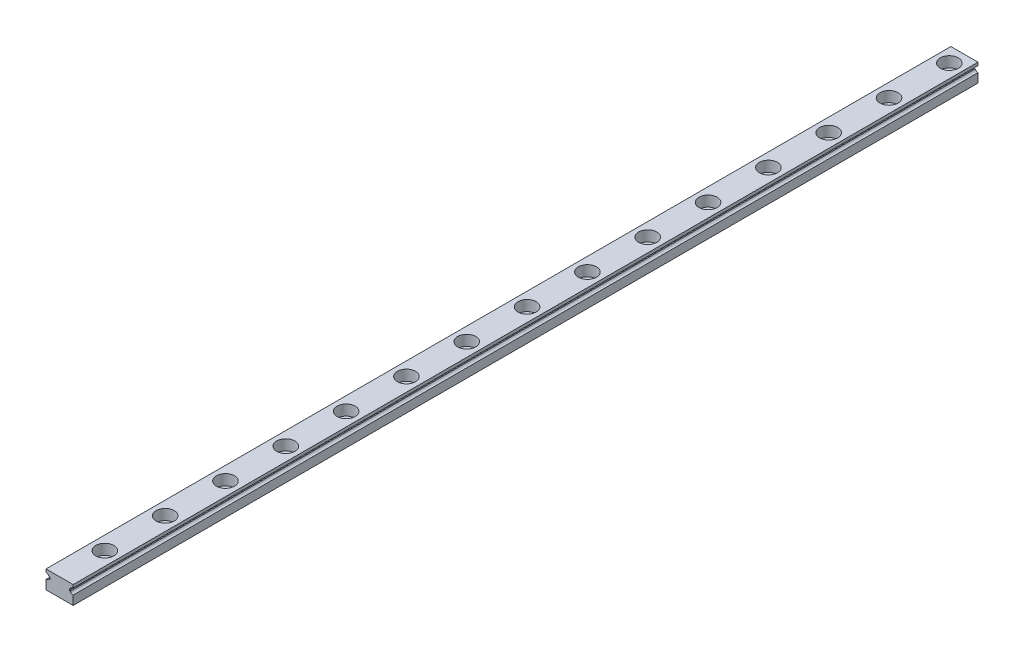
SolidWorks part; units mm, degrees
ref_plane "Спереди" through (0, 0, 0) normal (0, 0, 1) x (1, 0, 0)
ref_plane "Сверху" through (0, 0, 0) normal (0, 1, 0) x (1, 0, 0)
ref_plane "Справа" through (0, 0, 0) normal (1, 0, 0) x (0, 0, -1)
sketch "Sketch1" plane through (0, 0, 0) normal (0, 0, 1) x (1, 0, 0)
  line L0 (0, 0) -> (0, 5.7299) construction
  line L1 (-4.5, -3) -> (4.5, -3)
  line L2 (-4.5, -3) -> (-4.5, 0)
  line L3 (-4.5, 3) -> (4.5, 3)
  line L4 (4.5, -3) -> (4.5, 0)
  line L5 (-4.5, -3) -> (4.5, 3) construction
  line L6 (-4.5, 3) -> (4.5, -3) construction
  line L7 (-4.5, 2) -> (-4.5, 3)
  line L8 (-3.564, 0.648) -> (-3.2351, 0.648)
  line L9 (3.564, 0.648) -> (3.2351, 0.648)
  line L10 (-3.564, 1.352) -> (-3.2351, 1.352)
  line L11 (-3.2351, 0.648) -> (-3.2351, 1.352)
  line L12 (3.2351, 0.648) -> (3.2351, 1.352)
  line L13 (3.564, 1.352) -> (3.2351, 1.352)
  line L14 (4.5, 2) -> (4.5, 3)
  arc A0 (-3.564, 1.352) -> (-4.5, 2) centre (-4.5, 1) ccw
  arc A1 (-4.5, 0) -> (-3.564, 0.648) centre (-4.5, 1) ccw
  arc A2 (4.5, 0) -> (3.564, 0.648) centre (4.5, 1) cw
  arc A3 (3.564, 1.352) -> (4.5, 2) centre (4.5, 1) cw
  point P0 (0, 0)
  dimension "D3" = 1
  dimension "D1" = 9
  dimension "D2" = 6
  dimension "D4" = 2
extrude "Extrude1" add sketch "Sketch1" along normal blind 300
sketch "Sketch2" plane through (0, 3, 0) normal (0, 1, 0) x (1, 0, 0)
  line L0 (4.5, 0) -> (-4.5, 0) construction
  circle A0 centre (0, -5) radius 1.75
  circle A1 centre (0, -5) radius 3
  dimension "D1" = 3.5
  dimension "D2" = 6
  dimension "D3" = 5
extrude "Extrude2" cut sketch "Sketch2" against normal blind 3.5 contours A1
extrude "Extrude3" cut sketch "Sketch" against normal through all contours A0
sketch "Sketch" plane through (0, 3, 0) normal (0, 1, 0) x (1, 0, 0) same geometry as "Sketch2"
pattern_linear "LPattern1" count 15 spacing 20 along (0, 0, 1) of "Extrude2", "Extrude3"
